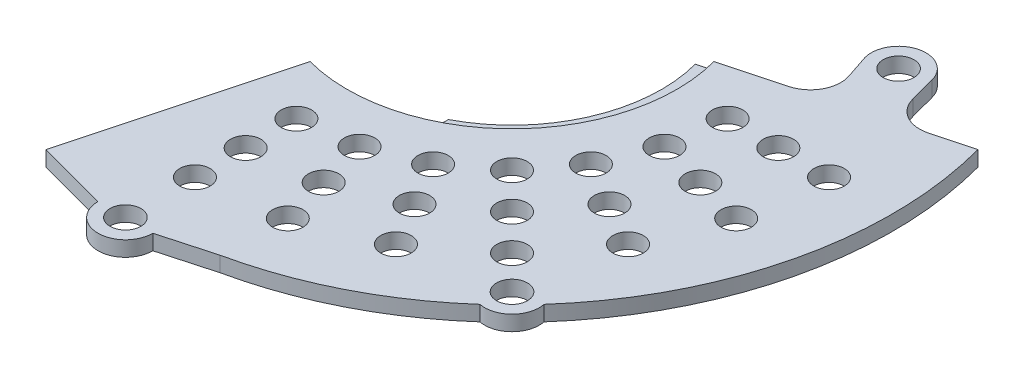
SolidWorks part; units mm, degrees
ref_plane "Front Plane" through (0, 0, 0) normal (0, 0, 1) x (1, 0, 0)
ref_plane "Top Plane" through (0, 0, 0) normal (0, 1, 0) x (1, 0, 0)
ref_plane "Right Plane" through (0, 0, 0) normal (1, 0, 0) x (0, 0, -1)
sketch "Sketch2" plane through (0, 0, 0) normal (0, 1, 0) x (1, 0, 0)
  line L0 (0, 0) -> (-19.4114, -72.4444)
  line L1 (0, 0) -> (72.4444, 19.4114)
  line L2 (0, 0) -> (0, -23.7748) construction
  line L3 (0, 0) -> (25.7561, 0) construction
  circle A0 centre (0, 0) radius 75
  circle A1 centre (0, 0) radius 32.5
  dimension "D1" = 15
  dimension "D3" = 150
  dimension "D2" = 15
extrude "Boss-Extrude2" add sketch "Sketch2" along normal blind 3 contours A1 L0 A0 L1 region at (33.0691, 0, 33.0691)
sketch "Sketch3" plane through (0, 0, 0) normal (0, -1, 0) x (1, 0, 0)
  line L0 (-8.4116, 31.3926) -> (0, 0)
  line L1 (0, 0) -> (31.3926, -8.4116)
  line L2 (-8.4116, 31.3926) -> (8.4116, 31.3926)
  line L3 (13.6265, 26.1642) -> (13.6265, 29.5054)
  line L4 (12.5, 30) -> (12.5, 17) construction
  circle A0 centre (0, 0) radius 32.5
  circle A1 centre (0, 0) radius 29.5
  arc M1 (-8.4116, 31.3926) -> (31.3926, -8.4116) centre (0, 0) cw
  dimension "D1" = 3
  dimension "D2" = 0
extrude "Boss-Extrude3" add sketch "Sketch3" against normal blind 1.5 contours L2 M1 | A1 L1 L3 M1 region at (0, 0, 31.8362) region at (30.0533, 0, -7.6143)
sketch "Sketch4" plane through (0, 3, 0) normal (0, 1, 0) x (1, 0, 0)
  line L0 (0, 0) -> (0, -87.0119) construction
  circle A0 centre (0, -42.5) radius 3
  circle A1 centre (0, -52.5) radius 3
  arc A2 (-8.4116, -31.3926) -> (8.4116, -31.3926) centre (0, 0) ccw construction
  circle A3 centre (0, -62.5) radius 3
  point P12 (0, -62.987)
  dimension "D1" = 6
  dimension "D2" = 6
  dimension "D3" = 10
  dimension "D4" = 42.5
  dimension "D5" = 10
extrude "Cut-Extrude1" cut sketch "Sketch4" against normal blind 10
pattern_circular "CirPattern2" count 7 every 15 about axis through (0, 3, 0) along (0, 1, 0) of "Cut-Extrude1"
sketch "Sketch5" plane through (0, 0, 0) normal (0, -1, 0) x (-1, 0, 0)
  line L5 (14.6226, -34.2017) -> (40.6226, -58.0492) construction
  line L6 (14.6226, -58.0492) -> (40.6226, -34.2017) construction
  line L7 (14.6226, -41.9242) -> (17.9026, -41.9242)
  line L9 (17.9026, -41.9242) -> (17.9026, -37.7493)
  line L10 (14.6226, -47.5242) -> (17.9026, -47.5242)
  line L11 (17.9026, -47.5242) -> (17.9026, -51.8405)
  line L12 (22.0226, -40.6571) -> (22.0226, -48.7913)
  line L13 (17.9026, -37.7493) -> (22.0226, -40.6571)
  line L14 (22.0226, -48.7913) -> (17.9026, -51.8405)
  line L15 (27.6226, -39.2726) -> (27.6226, -58.0492) construction
  line L16 (24.8693, -58.0492) -> (24.8693, -54.7492)
  line L17 (24.8693, -54.7492) -> (20.6945, -54.7492)
  line L18 (30.3759, -58.0492) -> (30.3759, -54.7492)
  line L19 (30.3759, -54.7492) -> (34.5507, -54.7492)
  line L20 (23.6056, -50.5492) -> (31.7399, -50.5492)
  line L21 (20.6945, -54.7492) -> (23.6056, -50.5492)
  line L22 (31.7399, -50.5492) -> (34.5507, -54.7492)
  point P0 (27.6226, -46.1255)
  point P17 (22.0226, -44.7242)
  point P20 (30.3759, -56.3992)
  dimension "D1" = 26
  dimension "D3" = 14.0912
  dimension "D4" = 3.28
  dimension "D5" = 5.6
  dimension "D6" = 3.28
  dimension "D8" = 8.1342
  dimension "D9" = 2.8
  dimension "D11" = 3.3
  dimension "D12" = 5.5066
  dimension "D15" = 4.1749
  dimension "D16" = 13.8562
  dimension "D19" = 3.3
  dimension "D22" = 2.7533
  dimension "D23" = 6.9281
sketch "Sketch7" plane through (0, 0, 0) normal (0, -1, 0) x (1, 0, 0)
  line L0 (-19.4114, 72.4444) -> (-5.4046, 76.2)
  line L1 (0, 81.6046) -> (0, 69.8583) construction
  line L2 (5.4046, 76.2) -> (15.7871, 73.3196)
  line L3 (49.1948, -13.1817) -> (45.5569, -24.0888)
  line L4 (28.4948, -7.6352) -> (72.4444, -19.4114) construction
  line L5 (56.0149, -26.8193) -> (58.9428, -15.7937)
  line L6 (49.1948, -13.1817) -> (50.2647, -9.9741)
  line L7 (50.2647, -9.9741) -> (58.9428, -12.8686)
  line L8 (58.9428, -12.8686) -> (58.9428, -15.7937)
  circle A1 centre (0, 0) radius 75
  circle A2 centre (0, 76.2) radius 5.4046
  circle A3 centre (0, 76.2) radius 3.0476
  circle A4 centre (50.8, 50.8) radius 5.4046
  circle A5 centre (50.8, 50.8) radius 3.0476
  circle A6 centre (50.8, -25.4) radius 5.4046
  circle A7 centre (50.8, -25.4) radius 3.0476
  line M30 (28.4948, -7.6352) -> (72.4444, -19.4114)
  arc M31 (72.4444, -19.4114) -> (-19.4114, 72.4444) centre (0, 0) ccw
extrude "Boss-Extrude5" add sketch "Sketch7" against normal up to surface (3 mm away) contours A2 L1 A3 A1 | L1 A2 A1 A3 | A2 L0 M31 | A2 L2 M31 | A6 L5 L3 M30 | L8 L7 L6 M30 | A4 | A6 | A7 region at (53.0592, 0, -18.0113) region at (54.1883, 0, -12.9386) region at (-8.8845, 0, 74.8394) region at (-2.9963, 0, 78.3875) region at (2.9963, 0, 78.3875) region at (8.447, 0, 74.9161) up to face at (43.9496, 3, 11.7763)
extrude "Cut-Extrude2" cut sketch "Sketch7<3>" against normal up to surface (3 mm away) contours A3 L1 M31 | L1 A3 A1 | L1 A3 M31 | L1 A1 A3 | A5 region at (-1.3593, 0, 76.8667) region at (-1.0986, 0, 74.2278) region at (1.3593, 0, 76.8667) region at (1.0986, 0, 74.2278) region at (50.8, 0, 50.8) up to face at (32.9855, 3, 26.6091)
sketch "Sketch7<3>" plane through (0, 0, 0) normal (0, -1, 0) x (1, 0, 0) same geometry as "Sketch7"
fillet "Fillet1" radius 6 2 edges at (49.1948, 1.5, -13.1817) (58.9428, 1.5, -15.7937)
